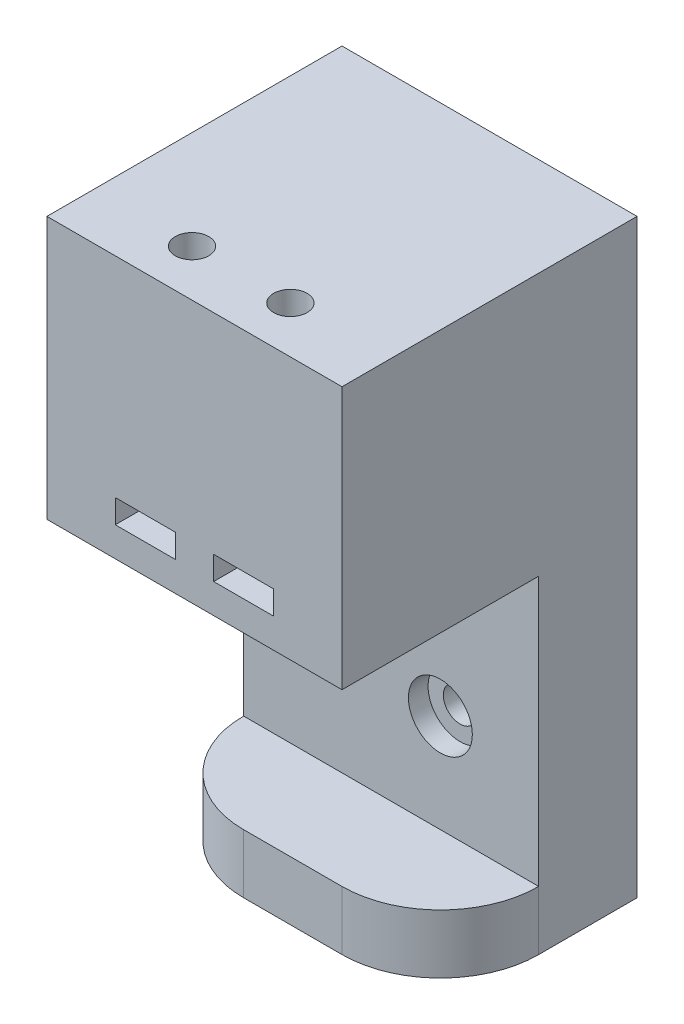
SolidWorks part; units mm, degrees
ref_plane "Plan de face" through (0, 0, 0) normal (0, 0, 1) x (1, 0, 0)
ref_plane "Plan de dessus" through (0, 0, 0) normal (0, 1, 0) x (1, 0, 0)
ref_plane "Plan de droite" through (0, 0, 0) normal (1, 0, 0) x (0, 0, -1)
sketch "Esquisse1" plane through (0, 0, 0) normal (0, 0, 1) x (1, 0, 0)
  line L1 (0, 0) -> (30, 0)
  line L2 (0, 0) -> (0, 60)
  line L3 (0, 60) -> (30, 60)
  line L4 (30, 0) -> (30, 60)
  dimension "D1" = 30
  dimension "D2" = 60
extrude "Boss.-Extru.1" add sketch "Esquisse1" along normal blind 10
sketch "Esquisse2" plane through (0, 0, 10) normal (0, 0, 1) x (1, 0, 0)
  line L0 (30, 0) -> (30, 60) construction
  line L1 (0, 0) -> (30, 0) construction
  line L2 (0, 60) -> (0, 0) construction
  line L3 (30, 0) -> (30, 6)
  line L4 (0, 0) -> (30, 0)
  line L5 (0, 6) -> (0, 0)
  line L6 (0, 6) -> (30, 6)
  dimension "D1" = 6
extrude "Boss.-Extru.2" add sketch "Esquisse2" along normal blind 10
sketch "Esquisse3" plane through (0, 0, 0) normal (0, -1, 0) x (1, 0, 0)
  line L0 (0, 20) -> (0, 0) construction
  line L1 (0, 0) -> (30, 0) construction
  circle A0 centre (15, 60) radius 4
  dimension "D3" = 8
  dimension "D1" = 15
  dimension "D2" = 60
extrude "Enlèv. mat.-Extru.1" [suppressed] cut sketch "Esquisse3" against normal up to surface (6 mm away) up to face at (15, 6, 15)
sketch "Esquisse4" plane through (0, 0, 10) normal (0, 0, 1) x (1, 0, 0)
  line L0 (30, 6) -> (30, 60) construction
  line L1 (30, 33.32) -> (30, 60)
  line L2 (0, 60) -> (0, 6) construction
  line L3 (30, 60) -> (0, 60) construction
  line L4 (0, 60) -> (0, 33.32)
  line L5 (30, 60) -> (0, 60)
  line L6 (0, 33.32) -> (30, 33.32)
  line L8 (30, 6) -> (0, 6) construction
  dimension "D1" = 27.32
extrude "Boss.-Extru.3" add sketch "Esquisse4" along normal blind 20
sketch "Esquisse5" plane through (0, 33.32, 0) normal (0, -1, 0) x (1, 0, 0)
  line L0 (0, 30) -> (0, 10) construction
  line L2 (0, 30) -> (30, 30) construction
  circle A0 centre (10, 25.25) radius 2.2
  circle A1 centre (20, 25.25) radius 2.2
  dimension "D3" = 4.4
  dimension "D4" = 4.4
  dimension "D1" = 10
  dimension "D2" = 10
  dimension "D5" = 4.75
  dimension "D6" = 4.75
hole_wizard "Dégagement M31" positions "Esquisse8" profile "Esquisse7" hole size "M3" standard "ISO"
sketch "Esquisse8" plane through (0, 33.32, 0) normal (0, -1, 0) x (-1, 0, 0)
  point P0 (-10, -25.25)
  point P3 (-20, -25.25)
sketch "Esquisse7" plane through (10, 33.32, 25.25) normal (1, 0, 0) x (0, 0, -1)
  line L0 (0, 0) -> (0, 27.7015)
  line L1 (0, 27.7015) -> (1.7, 26.68)
  line L2 (1.7, 26.68) -> (1.7, 0)
  line L5 (1.7, 0) -> (0, 0)
  line L10 (0, 27.7015) -> (-1.7, 26.68) construction
  line L11 (0, -6.35) -> (0, 107.95) construction
  dimension "Diamètre du perçage" = 3.4
  dimension "Profondeur du perçage" = 26.68
  dimension "Angle de pointe" = 118
sketch "Esquisse9" plane through (0, 0, 10) normal (0, 0, 1) x (1, 0, 0)
  line L0 (0, 33.32) -> (0, 6) construction
  line L1 (30, 6) -> (30, 33.32) construction
  line L2 (30, 6) -> (0, 6) construction
  line L3 (0, 33.32) -> (30, 33.32) construction
  circle A1 centre (20, 16) radius 1.5
  circle A2 centre (10, 23.32) radius 1.5
  dimension "D2" = 3
  dimension "D4" = 3
  dimension "D1" = 10
  dimension "D3" = 10
  dimension "D5" = 10
  dimension "D6" = 10
hole_wizard "Chambrage pour tête cylindrique fendue M31" positions "Esquisse10" profile "Esquisse12" counterbore size "M3" standard "ISO"
sketch "Esquisse10" plane through (0, 0, 10) normal (0, 0, 1) x (1, 0, 0)
  point P0 (10, 23.32)
  point P3 (20, 16)
sketch "Esquisse12" plane through (10, 23.32, 10) normal (1, 0, 0) x (0, -1, 0)
  line L0 (0, 0) -> (0, 11.0215)
  line L1 (0, 11.0215) -> (1.7, 10)
  line L2 (1.7, 10) -> (1.7, 2)
  line L3 (1.7, 2) -> (3.25, 2)
  line L4 (3.25, 2) -> (3.25, 0)
  line L5 (3.25, 0) -> (0, 0)
  line L10 (0, 11.0215) -> (-1.7, 10) construction
  line L11 (0, -6.35) -> (0, 107.95) construction
  dimension "Diamètre du perçage" = 3.4
  dimension "Profondeur du perçage" = 10
  dimension "Diamètre du chambrage" = 6.5
  dimension "Profondeur du chambrage" = 2
  dimension "Angle de pointe" = 118
fillet "Congé1" radius 10 2 edges at (30, 3, 20) (0, 3, 20)
sketch "Esquisse13" plane through (0, 0, 30) normal (0, 0, 1) x (1, 0, 0)
  line L0 (0, 33.32) -> (30, 33.32) construction
  line L1 (6.95, 38.72) -> (13.05, 38.72)
  line L2 (6.95, 38.72) -> (6.95, 36.32)
  line L3 (6.95, 36.32) -> (13.05, 36.32)
  line L4 (13.05, 38.72) -> (13.05, 36.32)
  line L5 (23.05, 38.72) -> (16.95, 38.72)
  line L6 (23.05, 38.72) -> (23.05, 36.32)
  line L7 (23.05, 36.32) -> (16.95, 36.32)
  line L8 (16.95, 38.72) -> (16.95, 36.32)
  line L9 (0, 60) -> (0, 33.32) construction
  line L10 (30, 33.32) -> (30, 60) construction
  point P10 (10, 38.72)
  point P13 (20, 38.72)
  dimension "D1" = 3
  dimension "D2" = 3
  dimension "D3" = 10
  dimension "D4" = 10
  dimension "D5" = 6.1
  dimension "D6" = 6.1
  dimension "D7" = 2.4
  dimension "D8" = 2.4
extrude "Enlèv. mat.-Extru.2" cut sketch "Esquisse13" against normal blind 8.45
equation "\"D4@Esquisse5\"=\"D3@Esquisse5\""
equation "\"D6@Esquisse5\"=\"D5@Esquisse5\""
